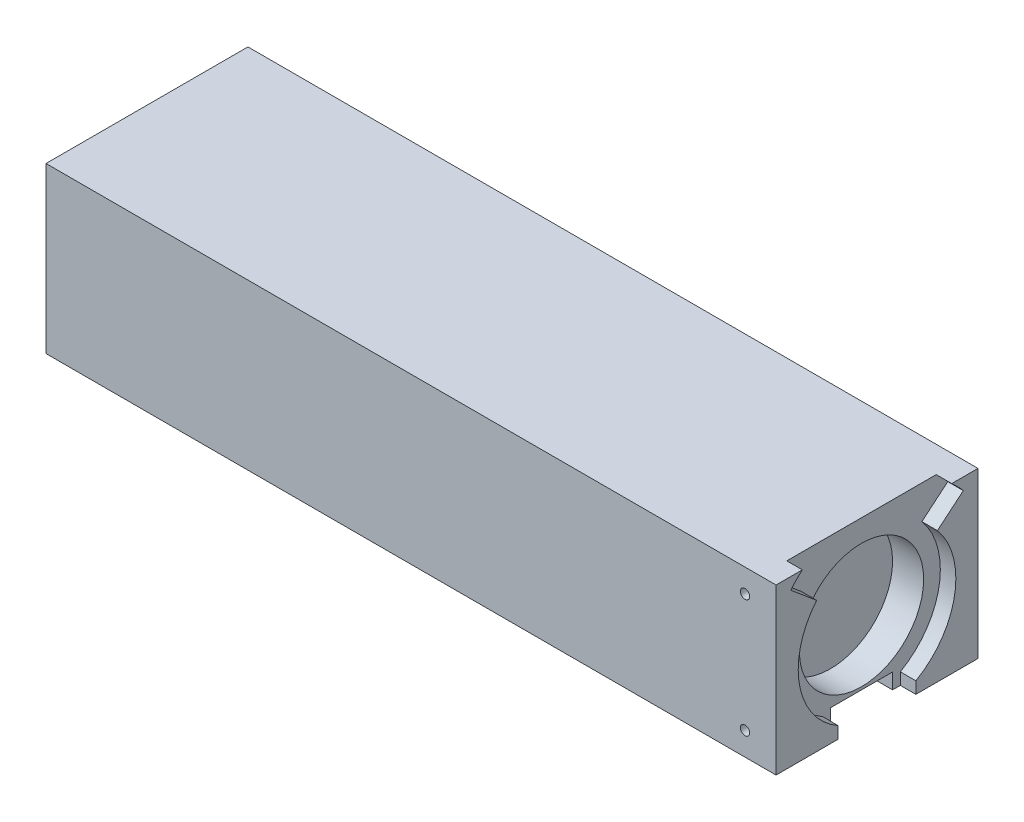
SolidWorks part; units mm, degrees
ref_plane "前视基准面" through (0, 0, 0) normal (0, 0, 1) x (1, 0, 0)
ref_plane "上视基准面" through (0, 0, 0) normal (0, 1, 0) x (1, 0, 0)
ref_plane "右视基准面" through (0, 0, 0) normal (1, 0, 0) x (0, 0, -1)
other "Configuration Table"
sketch "草图1" plane through (0, 0, 0) normal (0, 1, 0) x (1, 0, 0)
  line L1 (-47, -13) -> (47, -13)
  line L2 (-47, -13) -> (-47, 13)
  line L3 (-47, 13) -> (47, 13)
  line L4 (47, -13) -> (47, 13)
  line L5 (-47, -13) -> (47, 13) construction
  line L6 (-47, 13) -> (47, -13) construction
  circle A1 centre (-44, 10) radius 0.7
  circle A2 centre (-44, -10) radius 0.7
  circle A3 centre (44, 10) radius 0.7
  circle A4 centre (44, -10) radius 0.7
  point P0 (0, 0)
  dimension "D3" = 3
  dimension "D4" = 3
  dimension "D1" = 94
  dimension "D2" = 26
  dimension "D7" = 1.4
  dimension "D5" = 3
  dimension "D6" = 3
extrude "凸台-拉伸1" add sketch "草图1" along normal blind 21.2 contours L2 L3 L4 L1
extrude "切除-拉伸1" cut sketch "草图1<7>" along normal blind 3 contours A4 | A3 | A2 | A1
sketch "草图1<7>" plane through (0, 0, 0) normal (0, 1, 0) x (1, 0, 0) same geometry as "草图1"
sketch "草图2" plane through (0, 0, 0) normal (0, -1, 0) x (1, 0, 0)
  line L0 (-47, 13) -> (-47, -13) construction
  line L1 (-37, 10.7) -> (40.9, 10.7)
  line L2 (-37, 10.7) -> (-37, -10.7)
  line L3 (-37, -10.7) -> (40.9, -10.7)
  line L4 (40.9, 10.7) -> (40.9, -10.7)
  line L5 (47, 13) -> (47, -13) construction
  line L6 (-37, 0) -> (0, 0) construction
  line L7 (-47, 13) -> (47, 13) construction
  dimension "D1" = 10
  dimension "D2" = 6.1
  dimension "D3" = 2.3
extrude "切除-拉伸2" cut sketch "草图2" against normal offset from surface (19.3 mm away) 1.9 up to face at (0, 21.2, 0)
sketch "草图5" plane through (0, 0, 0) normal (0, -1, 0) x (1, 0, 0)
  line L0 (-37, 10.7) -> (-37, -10.7) construction
  line L1 (-37, 4) -> (-42.5, 4)
  line L2 (-37, 4) -> (-37, -4)
  line L3 (-37, -4) -> (-42.5, -4)
  line L4 (-42.5, 4) -> (-42.5, -4)
  line L5 (40.9, -10.7) -> (40.9, 10.7) construction
  line L6 (40.9, 4) -> (46.4, 4)
  line L7 (40.9, 4) -> (40.9, -4)
  line L8 (40.9, -4) -> (46.4, -4)
  line L9 (46.4, 4) -> (46.4, -4)
  line L10 (40.9, 0) -> (46.4, 0) construction
  line L11 (-47, 13) -> (47, 13) construction
  line L12 (-47, 13) -> (-47, -13) construction
  dimension "D1" = 9
  dimension "D2" = 4.5
extrude "切除-拉伸3" cut sketch "草图5" against normal blind 2 contours L3 L4 L1 L2 | L8 L9 L6 L7
sketch "草图6" plane through (0, 0, 0) normal (0, -1, 0) x (1, 0, 0)
  line L6 (-47, 13) -> (47, 13) construction
  line L7 (-36, 12) -> (40, 12)
  line L8 (-36, 12) -> (-36, -12)
  line L9 (-36, -12) -> (40, -12)
  line L10 (40, 12) -> (40, -12)
  line L11 (-47, -13) -> (47, -13) construction
  line L12 (47, 13) -> (47, -13) construction
  line L13 (-47, 13) -> (-47, -13) construction
  dimension "D1" = 1
  dimension "D2" = 1
  dimension "D3" = 7
  dimension "D4" = 11
extrude "切除-拉伸4" cut sketch "草图6" against normal blind 3
sketch "草图7" plane through (47, 0, 0) normal (1, 0, 0) x (0, 0, -1)
  line L2 (-13, 0) -> (13, 0) construction
  line L3 (-5, 1.517) -> (5, 1.517)
  line L4 (-5, 1.517) -> (-5, 0)
  line L5 (-5, 0) -> (5, 0)
  line L6 (5, 1.517) -> (5, 0)
  line L7 (-15.5432, 0.2) -> (16.0426, 0.2) construction
  circle A0 centre (0, 10.35) radius 10.15
  dimension "D1" = 20.3
  dimension "D2" = 0.2
  dimension "D3" = 10
extrude "切除-拉伸5" cut sketch "草图7" against normal blind 2 contours A0 | L6 L5 L4 L3
sketch "草图8" plane through (45, 0, 0) normal (1, 0, 0) x (0, 0, -1)
  circle A0 centre (0, 10.35) radius 8
  arc A1 (5, 1.517) -> (-5, 1.517) centre (0, 10.35) ccw construction
  dimension "D1" = 16
extrude "切除-拉伸6" cut sketch "草图8" against normal blind 4
sketch "草图9" plane through (47, 0, 0) normal (1, 0, 0) x (0, 0, -1)
  line L0 (0, 10.35) -> (11.1076, 19.6704)
  line L1 (0, 10.35) -> (-11.1076, 19.6704)
  line L2 (0, 10.35) -> (20.7679, 10.35) construction
  circle A0 centre (0, 10.35) radius 8 construction
  circle A1 centre (0, 10.35) radius 14.5
  line M10 (13, 21.2) -> (-13, 21.2)
  arc M14 (-5, 1.517) -> (5, 1.517) centre (0, 10.35) cw
  dimension "D1" = 29
  dimension "D2" = 40
  dimension "D3" = 40
extrude "切除-拉伸12" cut sketch "草图9" against normal blind 2 contours L1 L0 M14 | L0 A1 L1 M10 M14 region at (47, 16.2899, 0) region at (47, 20.7263, 0)
sketch "草图10" plane through (0, 0, -13) normal (0, 0, -1) x (-1, 0, 0)
  line L0 (47, 0) -> (-47, 0) construction
  line L1 (47, 21.2) -> (-47, 21.2) construction
  line L2 (-47, 21.2) -> (-47, 0) construction
  circle A0 centre (-43, 18.2) radius 0.6
  circle A1 centre (-43, 3) radius 0.6
  point P4 (0, 0)
  point P5 (0, 0)
  dimension "D1" = 1.2
  dimension "D2" = 3
  dimension "D3" = 3
  dimension "D4" = 4
extrude "切除-拉伸13" cut sketch "草图10" against normal blind 3 contours A0 | A1 region at (43, 18.2, -13)
extrude "切除-拉伸14" cut sketch "草图10<3>" along normal blind 3 from surface starting at face at (0, 10.6, 13)
sketch "草图10<3>" plane through (0, 0, -13) normal (0, 0, -1) x (-1, 0, 0) same geometry as "草图10"
sketch "草图11" plane through (0, 0, 0) normal (0, -1, 0) x (1, 0, 0)
  line L1 (-45.95, 8.15) -> (-43.45, 8.15)
  line L2 (-45.95, 8.15) -> (-45.95, -2.85)
  line L3 (-45.95, -2.85) -> (-43.45, -2.85)
  line L4 (-43.45, 8.15) -> (-43.45, -2.85)
  line L5 (-45.95, 2.65) -> (-43.45, 2.65) construction
  line L6 (-47, 13) -> (-47, -13) construction
  line L7 (-47, 13) -> (47, 13) construction
  point P6 (-44.7, 2.65)
  dimension "D1" = 2.5
  dimension "D2" = 11
  dimension "D3" = 2.3
  dimension "D4" = 10.35
extrude "切除-拉伸15" cut sketch "草图11" against normal blind 3
sketch "草图12" plane through (-47, 0, 0) normal (-1, 0, 0) x (0, 0, 1)
  line L0 (13, 0) -> (-13, 0) construction
  line L1 (-13, 21.2) -> (-13, 0) construction
  line L2 (13, 21.2) -> (13, 0) construction
  circle A0 centre (-8.05, 2) radius 0.3
  circle A1 centre (8.05, 2) radius 0.3
  dimension "D1" = 0.6
  dimension "D2" = 2
  dimension "D3" = 4.95
  dimension "D4" = 4.95
  dimension "D5" = 2
extrude "切除-拉伸16" cut sketch "草图12" against normal blind 3
sketch "草图13" plane through (-47, 0, 0) normal (-1, 0, 0) x (0, 0, 1)
  line L0 (13, 0) -> (-13, 0) construction
  line L1 (-6, 3) -> (6, 3)
  line L2 (-6, 3) -> (-6, 0)
  line L3 (-6, 0) -> (6, 0)
  line L4 (6, 3) -> (6, 0)
  line L5 (-13, 21.2) -> (-13, 0) construction
  line L6 (13, 21.2) -> (13, 0) construction
  dimension "D1" = 7
  dimension "D2" = 7
  dimension "D3" = 3
extrude "切除-拉伸17" cut sketch "草图13" against normal blind 11
